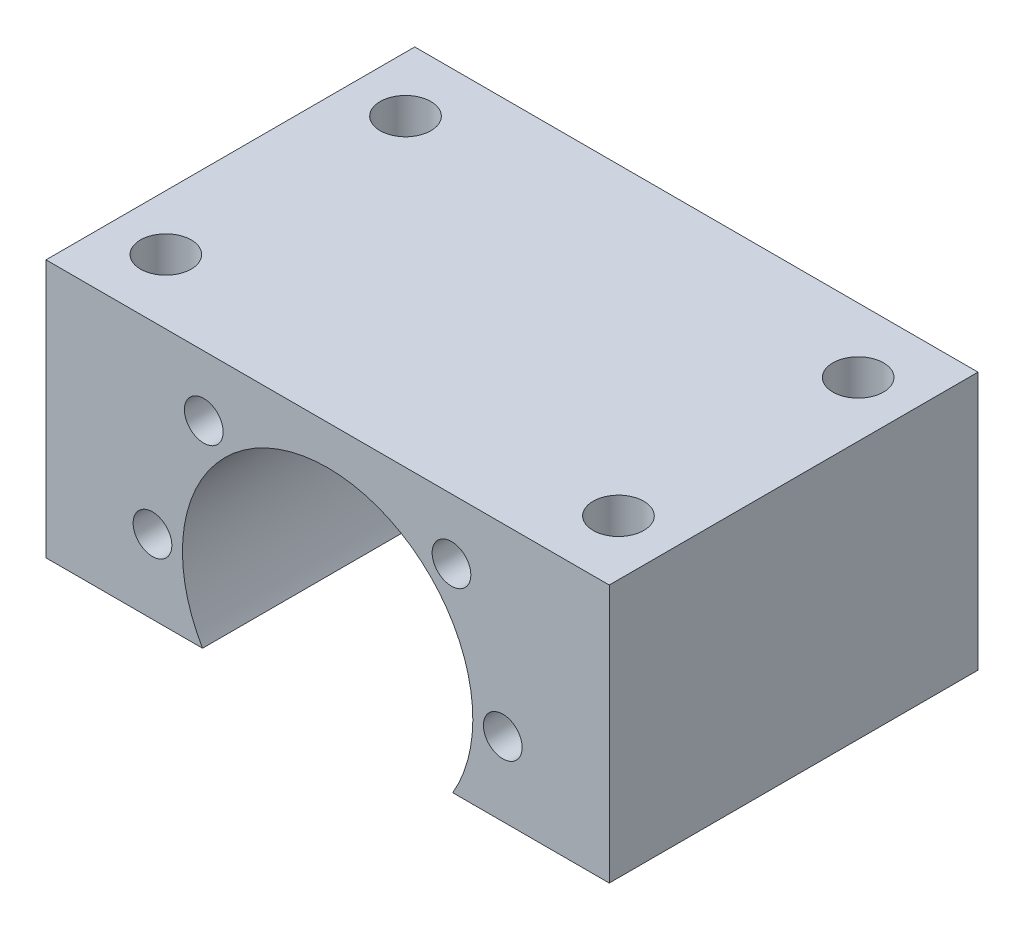
SolidWorks part; units mm, degrees
ref_plane "Front Plane" through (0, 0, 0) normal (0, 0, 1) x (1, 0, 0)
ref_plane "Top Plane" through (0, 0, 0) normal (0, 1, 0) x (1, 0, 0)
ref_plane "Right Plane" through (0, 0, 0) normal (1, 0, 0) x (0, 0, -1)
sketch "Sketch1" plane through (0, 0, 0) normal (0, 0, 1) x (1, 0, 0)
  line L0 (13.2665, 40) -> (-13.2665, 40) construction
  line L1 (13.2665, 40) -> (-13.2665, 40)
  line L4 (27.55, 40) -> (13.2665, 40)
  line L5 (-27.55, 12) -> (-30.55, 12)
  line L7 (-27.55, 40) -> (-13.2665, 40)
  line L9 (-30.55, 12) -> (-30.55, 40)
  line L10 (-27.55, 12) -> (-13.567, 12)
  line L11 (27.55, 12) -> (13.567, 12)
  line L12 (-30.55, 40) -> (-27.55, 40)
  line L13 (27.55, 40) -> (30.55, 40)
  line L14 (30.55, 40) -> (30.55, 12)
  line L15 (30.55, 12) -> (27.55, 12)
  circle A3 centre (-13.435, 33.435) radius 2.1
  circle A7 centre (19, 20) radius 2.1
  circle A8 centre (13.435, 33.435) radius 2.1
  circle A9 centre (-19, 20) radius 2.1
  arc A11 (13.567, 12) -> (-13.567, 12) centre (0, 20) ccw
extrude "Boss-Extrude1" add sketch "Sketch1" against normal up to surface (40 mm away)
sketch "Sketch2" plane through (0, 40, 0) normal (0, 1, 0) x (1, 0, 0)
  circle A0 centre (-24.55, 7) radius 2.75
  circle A1 centre (-24.55, 33) radius 2.75
  circle A2 centre (24.55, 33) radius 2.75
  circle A3 centre (24.55, 7) radius 2.75
extrude "Cut-Extrude1" cut sketch "Sketch2" against normal blind 50 contours A1 | A0 | A3 | A2 region at (-24.55, 40, -7) region at (-24.55, 40, -33) region at (24.55, 40, -33) region at (24.55, 40, -7)
